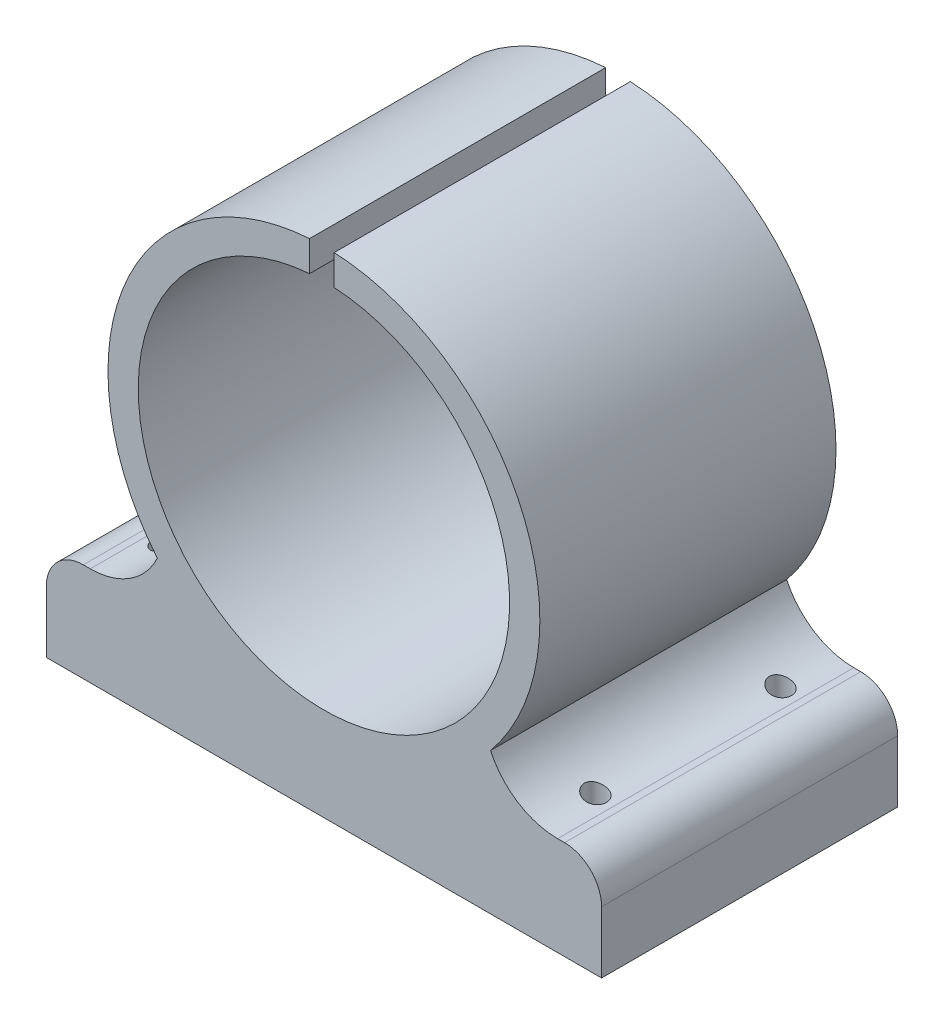
SolidWorks part; units mm, degrees
ref_plane "Front" through (0, 0, 0) normal (0, 0, 1) x (1, 0, 0)
ref_plane "Top" through (0, 0, 0) normal (0, 1, 0) x (1, 0, 0)
ref_plane "Right" through (0, 0, 0) normal (1, 0, 0) x (0, 0, -1)
sketch "Sketch1" plane through (0, 0, 0) normal (0, 0, 1) x (1, 0, 0)
  line L0 (-28.575, 0) -> (28.575, 0)
  line L1 (-28.575, 0) -> (-28.575, 10.16)
  line L2 (-28.575, 10.16) -> (-17.145, 10.16)
  line L3 (-17.145, 10.16) -> (-17.145, 14.5599)
  line L4 (0, 28.702) -> (0, 9.5931) construction
  line L5 (28.575, 0) -> (28.575, 10.16)
  line L6 (28.575, 10.16) -> (17.145, 10.16)
  line L7 (17.145, 10.16) -> (17.145, 14.5599)
  line L10 (-1.4817, 50.8776) -> (-1.4817, 47.7534)
  line L12 (1.0582, 50.9018) -> (1.0582, 47.7816)
  arc A0 (-1.4817, 47.7534) -> (1.0582, 47.7816) centre (0, 28.702) ccw
  arc A1 (17.145, 14.5599) -> (1.0582, 50.9018) centre (0, 28.702) ccw
  arc A2 (-1.4817, 50.8776) -> (-17.145, 14.5599) centre (0, 28.702) ccw
  point P3 (0, 0)
  dimension "D2" = 19.1089
  dimension "D4" = 44.45
  dimension "D1" = 57.15
  dimension "D3" = 28.702
  dimension "D5" = 10.16
  dimension "D6" = 11.43
  dimension "D7" = 2.54
  dimension "D8" = 3.1242
extrude "Boss-Extrude1" add sketch "Sketch1" along normal blind 30.48
fillet "Fillet1" radius 7.62 2 edges at (-17.145, 10.16, 15.24) (17.145, 10.16, 15.24)
fillet "Fillet2" radius 3.81 2 edges at (-28.575, 10.16, 15.24) (28.575, 10.16, 15.24)
sketch "Sketch2" plane through (0, 0, 0) normal (0, -1, 0) x (1, 0, 0)
  line L1 (-22.225, 24.765) -> (22.225, 24.765) construction
  line L2 (-22.225, 24.765) -> (-22.225, 5.715) construction
  line L3 (-22.225, 5.715) -> (22.225, 5.715) construction
  line L4 (22.225, 24.765) -> (22.225, 5.715) construction
  circle A0 centre (-22.225, 5.715) radius 1.143
  circle A1 centre (-22.225, 24.765) radius 1.143
  circle A2 centre (22.225, 24.765) radius 1.143
  circle A3 centre (22.225, 5.715) radius 1.143
  point P4 (0, 5.715)
  dimension "D4" = 2.286
  dimension "D1" = 19.05
  dimension "D2" = 44.45
  dimension "0.10" = 5.715
extrude "Cut-Extrude1" cut sketch "Sketch2" against normal up to next
